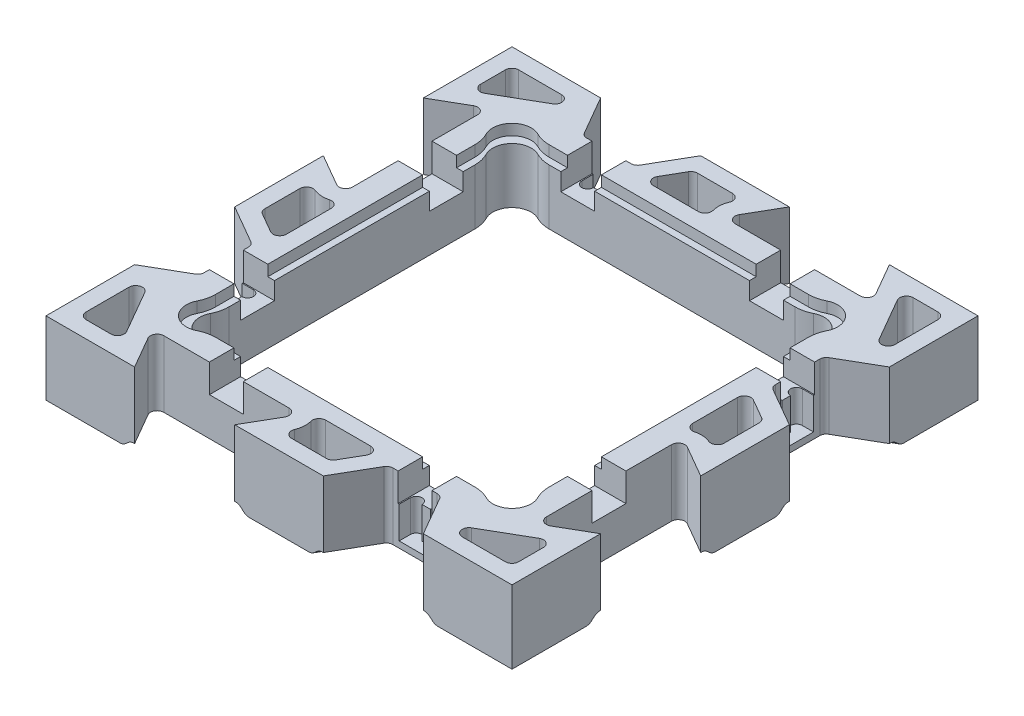
SolidWorks part; units mm, degrees
material "Macor"
ref_plane "Front Plane" through (0, 0, 0) normal (0, 0, 1) x (1, 0, 0)
ref_plane "Top Plane" through (0, 0, 0) normal (0, 1, 0) x (1, 0, 0)
ref_plane "Right Plane" through (0, 0, 0) normal (1, 0, 0) x (0, 0, -1)
sketch "Sketch1" plane through (0, 0, 0) normal (0, 1, 0) x (1, 0, 0)
  line L1 (-69.85, -69.85) -> (69.85, -69.85)
  line L2 (-69.85, -69.85) -> (-69.85, 69.85)
  line L3 (-69.85, 69.85) -> (69.85, 69.85)
  line L4 (69.85, -69.85) -> (69.85, 69.85)
  line L5 (-69.85, -69.85) -> (69.85, 69.85) construction
  line L6 (-69.85, 69.85) -> (69.85, -69.85) construction
  point P0 (0, 0)
  dimension "D1" = 139.7
extrude "Boss-Extrude1" add sketch "Sketch1" along normal mid plane 21.9
sketch "Sketch6" plane through (0, 10.95, 0) normal (0, 1, 0) x (1, 0, 0)
  line L0 (-48, 39.8683) -> (-48, -39.8683)
  line L1 (-48, -48) -> (48, -48) construction
  line L2 (-48, -48) -> (-48, 48) construction
  line L3 (-48, 48) -> (48, 48) construction
  line L4 (48, -48) -> (48, 48) construction
  line L5 (-48, -48) -> (48, 48) construction
  line L6 (-48, 48) -> (48, -48) construction
  line L7 (-39.8683, -48) -> (39.8683, -48)
  line L8 (39.8683, 48) -> (-39.8683, 48)
  line L9 (48, 39.8683) -> (48, -39.8683)
  arc A0 (-39.8683, 48) -> (-48, 39.8683) centre (-43.9341, 43.9341) ccw
  arc A1 (48, 39.8683) -> (39.8683, 48) centre (43.9341, 43.9341) ccw
  arc A2 (39.8683, -48) -> (48, -39.8683) centre (43.9341, -43.9341) ccw
  arc A3 (-48, -39.8683) -> (-39.8683, -48) centre (-43.9341, -43.9341) ccw
  point P0 (0, 0)
  point P21 (0, 0)
  dimension "D2" = 5.75
  dimension "D1" = 96
  dimension "D3" = 4
extrude "power_supply_component_depth" cut sketch "Sketch6" against normal through all both and the other way through all
ref_axis "Axis1" through (0, -25.4398, 0) along (0, 1, 0)
sketch "Sketch4" plane through (0, 10.95, 0) normal (0, 1, 0) x (1, 0, 0)
  line L0 (-43.2833, -69.85) -> (-50.5002, -57.35)
  line L1 (-69.85, -69.85) -> (69.85, -69.85) construction
  line L2 (-50.5002, -57.35) -> (-6.0665, -57.35)
  line L3 (-6.0665, -57.35) -> (-13.2833, -69.85)
  line L4 (-13.2833, -69.85) -> (-43.2833, -69.85)
  line L5 (43.2833, -69.85) -> (36.0665, -57.35)
  line L24 (43.2833, -69.85) -> (13.2833, -69.85)
  line L25 (-69.85, -69.85) -> (-43.2833, -69.85) construction
  line L26 (-13.2833, -69.85) -> (13.2833, -69.85) construction
  line L27 (43.2833, -69.85) -> (69.85, -69.85) construction
  line L28 (36.0665, -57.35) -> (20.5002, -57.35)
  line L30 (13.2833, -69.85) -> (20.5002, -57.35)
  dimension "D1" = 60
  dimension "D2" = 30
  dimension "D3" = 12.5
  dimension "D4" = 60
  dimension "D5" = 26.5667
extrude "Cut-Extrude6" cut sketch "Sketch4" against normal blind 22.4
sketch "Sketch8" plane through (0, 10.95, 0) normal (0, 1, 0) x (1, 0, 0)
  line L0 (-28.2833, -57.35) -> (-28.2833, -52.675) construction
  line L2 (28.2833, -57.35) -> (28.2833, -52.675) construction
  line L3 (36.0665, -57.35) -> (20.5002, -57.35) construction
  line L4 (-6.0665, -57.35) -> (-50.5002, -57.35) construction
  line L5 (-33.3633, -57.35) -> (-23.2033, -57.35)
  line L6 (-33.3633, -57.35) -> (-33.3633, -48)
  line L7 (-33.3633, -48) -> (-23.2033, -48)
  line L8 (-23.2033, -57.35) -> (-23.2033, -48)
  line L9 (-33.3633, -57.35) -> (-23.2033, -48) construction
  line L10 (-33.3633, -48) -> (-23.2033, -57.35) construction
  line L12 (23.2033, -57.35) -> (33.3633, -57.35)
  line L13 (23.2033, -57.35) -> (23.2033, -48)
  line L14 (23.2033, -48) -> (33.3633, -48)
  line L15 (33.3633, -57.35) -> (33.3633, -48)
  line L16 (23.2033, -57.35) -> (33.3633, -48) construction
  line L17 (23.2033, -48) -> (33.3633, -57.35) construction
  line L18 (-39.8683, -48) -> (39.8683, -48) construction
  dimension "D1" = 10.16
extrude "Cut-Extrude7" cut sketch "Sketch8" against normal blind 8.48
sketch "Sketch9" plane through (0, 2.47, 0) normal (0, 1, 0) x (1, 0, 0)
  line L0 (28.2833, -57.35) -> (28.2833, -55.6625) construction
  line L2 (27.0183, -53.975) -> (29.5483, -53.975)
  line L3 (23.5183, -53.975) -> (33.0483, -53.975) construction
  line L4 (23.5183, -53.975) -> (23.5183, -57.35)
  line L5 (23.5183, -57.35) -> (33.0483, -57.35)
  line L6 (33.0483, -53.975) -> (33.0483, -57.35)
  line L7 (23.5183, -53.975) -> (33.0483, -57.35) construction
  line L8 (23.5183, -57.35) -> (33.0483, -53.975) construction
  line L9 (23.2033, -57.35) -> (33.3633, -57.35) construction
  arc A0 (23.5183, -53.975) -> (27.0183, -53.975) centre (25.2683, -53.975) cw
  arc A1 (33.0483, -53.975) -> (29.5483, -53.975) centre (31.2983, -53.975) ccw
  dimension "D3" = 1.75
  dimension "D1" = 9.53
  dimension "D2" = 3.375
extrude "Cut-Extrude8" cut sketch "Sketch9" against normal blind 9.53
fillet "Fillet2" radius 2 4 edges at (20.5002, 0, 57.35) (36.0665, 0, 57.35) (-6.0665, 0, 57.35) (-50.5002, 0, 57.35)
pattern_circular "CirPattern5" count 4 over 360 about axis through (0, -25.4398, 0) along (0, 1, 0) of "Cut-Extrude6", "Cut-Extrude7", "Cut-Extrude8", "Fillet2"
sketch "Sketch10" plane through (0, 10.95, 0) normal (0, 1, 0) x (1, 0, 0)
  line L0 (-41.8683, 50) -> (41.8683, 50)
  line L1 (-50, -50) -> (50, -50) construction
  line L2 (-50, -50) -> (-50, 50) construction
  line L3 (-50, 50) -> (50, 50) construction
  line L4 (50, -50) -> (50, 50) construction
  line L5 (-50, -50) -> (50, 50) construction
  line L6 (-50, 50) -> (50, -50) construction
  line L7 (50, 41.8683) -> (50, -41.8683)
  line L8 (41.8683, -50) -> (-41.8683, -50)
  line L9 (-50, -41.8683) -> (-50, 41.8683)
  arc A0 (41.8683, 50) -> (50, 41.8683) centre (45.9341, 45.9341) cw
  arc A1 (50, -41.8683) -> (41.8683, -50) centre (45.9341, -45.9341) cw
  arc A2 (-41.8683, -50) -> (-50, -41.8683) centre (-45.9341, -45.9341) cw
  arc A3 (-50, 41.8683) -> (-41.8683, 50) centre (-45.9341, 45.9341) cw
  point P0 (0, 0)
  point P21 (0, 0)
  dimension "D2" = 5.75
  dimension "D1" = 100
  dimension "D3" = 4
extrude "Cut-Extrude9" cut sketch "Sketch10" against normal blind 3.25
fillet "Fillet3" radius 10 16 edges at (-50, 9.325, 41.8683) (-41.8683, 9.325, -50) (-50, 9.325, -41.8683) (50, 9.325, -41.8683) (41.8683, 9.325, -50) (-41.8683, 9.325, 50) (-39.8683, -1.625, -48) (39.8683, -1.625, -48) (48, -1.625, -39.8683) (48, -1.625, 39.8683) (-39.8683, -1.625, 48) (-48, -1.625, 39.8683) (-48, -1.625, -39.8683) (39.8683, -1.625, 48) (41.8683, 9.325, 50) (50, 9.325, 41.8683)
ref_plane "Plane1" through (19.4251, 0, 33.6453) normal (-0.5, 0, -0.866) x (-0.866, 0, 0.5)
sketch "Sketch11" plane through (19.4251, 0, 33.6453) normal (-0.5, 0, -0.866) x (-0.866, 0, 0.5)
  line L0 (72.4095, -10.95) -> (75.4095, -10.95)
  line L1 (75.4095, -10.95) -> (73.4095, -8.95)
  line L2 (73.4095, -8.95) -> (72.4095, -8.95)
  line L3 (72.4095, -10.95) -> (72.4095, 10.95) construction
  line L4 (72.4095, -8.95) -> (72.4095, -10.95)
  dimension "D1" = 3
  dimension "D2" = 2
  dimension "D3" = 45
  dimension "D4" = 1
sketch "Sketch12" plane through (0, -10.95, 0) normal (0, -1, 0) x (1, 0, 0)
  line L0 (-47.0361, 57.35) -> (-9.5306, 57.35) construction
  line L1 (-7.7985, 60.35) -> (-13.2833, 69.85) construction
  line L2 (-43.2833, 69.85) -> (-48.7682, 60.35) construction
  line L3 (-47.0361, 57.35) -> (-9.5306, 57.35)
  line L4 (-7.7985, 60.35) -> (-13.2833, 69.85)
  line L5 (-43.2833, 69.85) -> (-48.7682, 60.35)
  arc A0 (-9.5306, 57.35) -> (-7.7985, 60.35) centre (-9.5306, 59.35) ccw construction
  arc A1 (-48.7682, 60.35) -> (-47.0361, 57.35) centre (-47.0361, 59.35) ccw construction
  arc A2 (-9.5306, 57.35) -> (-7.7985, 60.35) centre (-9.5306, 59.35) ccw
  arc A3 (-48.7682, 60.35) -> (-47.0361, 57.35) centre (-47.0361, 59.35) ccw
sweep "Cut-Sweep1" cut profiles "Sketch11" path "Sketch12"
ref_plane "Plane2" through (-26.9251, 0, 46.6356) normal (0.5, 0, -0.866) x (-0.866, 0, -0.5)
sketch "Sketch13" plane through (-26.9251, 0, 46.6356) normal (0.5, 0, -0.866) x (-0.866, 0, -0.5)
  line L0 (-46.4287, -10.95) -> (-43.4287, -10.95)
  line L1 (-43.4287, -10.95) -> (-45.4287, -8.95)
  line L2 (-45.4287, -8.95) -> (-46.4287, -8.95)
  line L3 (-46.4287, -10.95) -> (-46.4287, 10.95) construction
  line L4 (-46.4287, -8.95) -> (-46.4287, -10.95)
  dimension "D1" = 45
  dimension "D2" = 2
  dimension "D3" = 3
sketch "Sketch14" plane through (0, -10.95, 0) normal (0, -1, 0) x (1, 0, 0)
  line L0 (36.6438, 58.35) -> (43.2833, 69.85) construction
  line L1 (21.6549, 57.35) -> (34.9118, 57.35) construction
  line L2 (13.2833, 69.85) -> (19.9229, 58.35) construction
  line L3 (36.6438, 58.35) -> (43.2833, 69.85)
  line L4 (21.6549, 57.35) -> (34.9118, 57.35)
  line L5 (13.2833, 69.85) -> (19.9229, 58.35)
  line L6 (13.2833, 69.85) -> (7.5098, 79.85)
  line L7 (43.2833, 69.85) -> (49.0568, 79.85)
  arc A0 (34.9118, 57.35) -> (36.6438, 58.35) centre (34.9118, 59.35) ccw construction
  arc A1 (19.9229, 58.35) -> (21.6549, 57.35) centre (21.6549, 59.35) ccw construction
  arc A2 (34.9118, 57.35) -> (36.6438, 58.35) centre (34.9118, 59.35) ccw
  arc A3 (19.9229, 58.35) -> (21.6549, 57.35) centre (21.6549, 59.35) ccw
  dimension "D1" = 10
sweep "Cut-Sweep2" cut profiles "Sketch13" path "Sketch14"
pattern_circular "CirPattern6" count 4 over 360 about axis through (0, -25.4398, 0) along (0, 1, 0) of "Cut-Sweep1", "Cut-Sweep2"
sketch "Sketch15" plane through (0, 0, 0) normal (0, 0, 1) x (1, 0, 0)
  line L0 (-48, -10.95) -> (-48, 7.7) construction
  line L1 (-48, -10.95) -> (-48, 7.7) construction
  line L2 (-48, -10.95) -> (-51, -10.95)
  line L3 (-51, -10.95) -> (-49, -8.95)
  line L4 (-49, -8.95) -> (-48, -8.95)
  line L5 (-48, -8.95) -> (-48, -10.95)
  dimension "D1" = 2
  dimension "D2" = 3
  dimension "D3" = 45
sketch "Sketch16" plane through (0, -10.95, 0) normal (0, -1, 0) x (1, 0, 0)
  line L0 (48, 36.848) -> (48, -36.848) construction
  line L1 (-36.848, 48) -> (36.848, 48) construction
  line L2 (-48, -36.848) -> (-48, 36.848) construction
  line L3 (36.848, -48) -> (-36.848, -48) construction
  line L4 (48, 36.848) -> (48, -36.848)
  line L5 (-36.848, 48) -> (36.848, 48)
  line L6 (-48, -36.848) -> (-48, 36.848)
  line L7 (36.848, -48) -> (-36.848, -48)
  arc A0 (48, -36.848) -> (49.0693, -41.3471) centre (58, -36.848) ccw construction
  arc A1 (49.0693, 41.3471) -> (48, 36.848) centre (58, 36.848) ccw construction
  arc A2 (49.0693, 41.3471) -> (41.3471, 49.0693) centre (43.9341, 43.9341) ccw construction
  arc A3 (36.848, 48) -> (41.3471, 49.0693) centre (36.848, 58) ccw construction
  arc A4 (-41.3471, 49.0693) -> (-36.848, 48) centre (-36.848, 58) ccw construction
  arc A5 (-41.3471, 49.0693) -> (-49.0693, 41.3471) centre (-43.9341, 43.9341) ccw construction
  arc A6 (-48, 36.848) -> (-49.0693, 41.3471) centre (-58, 36.848) ccw construction
  arc A7 (-49.0693, -41.3471) -> (-48, -36.848) centre (-58, -36.848) ccw construction
  arc A8 (-49.0693, -41.3471) -> (-41.3471, -49.0693) centre (-43.9341, -43.9341) ccw construction
  arc A9 (-36.848, -48) -> (-41.3471, -49.0693) centre (-36.848, -58) ccw construction
  arc A10 (41.3471, -49.0693) -> (36.848, -48) centre (36.848, -58) ccw construction
  arc A11 (41.3471, -49.0693) -> (49.0693, -41.3471) centre (43.9341, -43.9341) ccw construction
  arc A12 (48, -36.848) -> (49.0693, -41.3471) centre (58, -36.848) ccw
  arc A13 (49.0693, 41.3471) -> (48, 36.848) centre (58, 36.848) ccw
  arc A14 (49.0693, 41.3471) -> (41.3471, 49.0693) centre (43.9341, 43.9341) ccw
  arc A15 (36.848, 48) -> (41.3471, 49.0693) centre (36.848, 58) ccw
  arc A16 (-41.3471, 49.0693) -> (-36.848, 48) centre (-36.848, 58) ccw
  arc A17 (-41.3471, 49.0693) -> (-49.0693, 41.3471) centre (-43.9341, 43.9341) ccw
  arc A18 (-48, 36.848) -> (-49.0693, 41.3471) centre (-58, 36.848) ccw
  arc A19 (-49.0693, -41.3471) -> (-48, -36.848) centre (-58, -36.848) ccw
  arc A20 (-49.0693, -41.3471) -> (-41.3471, -49.0693) centre (-43.9341, -43.9341) ccw
  arc A21 (-36.848, -48) -> (-41.3471, -49.0693) centre (-36.848, -58) ccw
  arc A22 (41.3471, -49.0693) -> (36.848, -48) centre (36.848, -58) ccw
  arc A23 (41.3471, -49.0693) -> (49.0693, -41.3471) centre (43.9341, -43.9341) ccw
sweep "Cut-Sweep3" cut profiles "Sketch15" path "Sketch16"
fillet "Fillet4" radius 2 122 edges at (-46.3144, -10.95, -69.1) (-42.5616, -10.95, -62.6) (-37.4118, -10.95, -55.0199) (-13.572, -10.95, -63.35) (-19.1549, -10.95, -55.0199) (-44.2937, -8.95, -69.6) (-40.8296, -8.95, -63.6) (-36.4118, -8.95, -56.7519) (-15.5927, -8.95, -63.85) (-20.1549, -8.95, -56.7519) (49.0568, -10.95, -65.85) (51.3662, -10.95, -56.85) (7.5098, -10.95, -65.85) (5.2004, -10.95, -56.85) (47.0361, -8.95, -65.35) (49.6342, -8.95, -57.85) (9.5306, -8.95, -65.35) (6.9325, -8.95, -57.85) (69.1, -10.95, -46.3144) (62.6, -10.95, -42.5616) (55.0199, -10.95, -37.4118) (54.35, -10.95, -28.2833) (55.0199, -10.95, -19.1549) (69.6, -8.95, -44.2937) (63.6, -8.95, -40.8296) (56.7519, -8.95, -36.4118) (56.35, -8.95, -28.2833) (56.7519, -8.95, -20.1549) (65.85, -10.95, 7.5098) (56.85, -10.95, 5.2004) (54.35, -10.95, 28.2833) (56.85, -10.95, 51.3662) (65.35, -8.95, 9.5306) (57.85, -8.95, 6.9325) (56.35, -8.95, 28.2833) (57.85, -8.95, 49.6342) (46.3144, -10.95, 69.1) (42.5616, -10.95, 62.6) (37.4118, -10.95, 55.0199) (28.2833, -10.95, 54.35) (19.1549, -10.95, 55.0199) (44.2937, -8.95, 69.6) (40.8296, -8.95, 63.6) (36.4118, -8.95, 56.7519) (28.2833, -8.95, 56.35) (20.1549, -8.95, 56.7519) (-49.0568, -10.95, 65.85) (-51.3662, -10.95, 56.85) (-28.2833, -10.95, 54.35) (-7.5098, -10.95, 65.85) (-47.0361, -8.95, 65.35) (-49.6342, -8.95, 57.85) (-28.2833, -8.95, 56.35) (-9.5306, -8.95, 65.35) (-49.2439, -8.95, -38.929) (-48.7071, -8.95, -48.7071) (-38.929, -8.95, -49.2439) (0, -8.95, -49) (38.929, -8.95, -49.2439) (48.7071, -8.95, -48.7071) (49.2439, -8.95, -38.929) (49, -8.95, 0) (49.2439, -8.95, 38.929) (48.7071, -8.95, 48.7071) (38.929, -8.95, 49.2439) (0, -8.95, 49) (-38.929, -8.95, 49.2439) (-48.7071, -8.95, 48.7071) (-49.2439, -8.95, 38.929) (-49, -8.95, 18.424) (-51.1897, -10.95, -38.4665) (-50.1213, -10.95, -50.1213) (-38.4665, -10.95, -51.1897) (0, -10.95, -51) (38.4665, -10.95, -51.1897) (50.1213, -10.95, -50.1213) (51.1897, -10.95, -38.4665) (51, -10.95, 0) (51.1897, -10.95, 38.4665) (50.1213, -10.95, 50.1213) (38.4665, -10.95, 51.1897) (0, -10.95, 51) (-38.4665, -10.95, 51.1897) (-50.1213, -10.95, 50.1213) (-51.1897, -10.95, 38.4665) (-51, -10.95, 18.424) (-65.85, -10.95, -49.0568) (-56.85, -10.95, -51.3662) (-54.35, -10.95, -28.2833) (-65.85, -10.95, -7.5098) (-63.35, -10.95, 13.572) (-55.0199, -10.95, 19.1549) (-69.1, -10.95, 46.3144) (-62.6, -10.95, 42.5616) (-55.0199, -10.95, 37.4118) (-63.85, -8.95, 15.5927) (-56.7519, -8.95, 20.1549) (-69.6, -8.95, 44.2937) (-63.6, -8.95, 40.8296) (-56.7519, -8.95, 36.4118) (-65.35, -8.95, -47.0361) (-57.85, -8.95, -49.6342) (-65.35, -8.95, -9.5306) (-57.85, -8.95, -6.9325) (-28.2833, -10.95, -54.35) (-28.2833, -8.95, -56.35) (28.2833, -10.95, -54.35) (28.2833, -8.95, -56.35) (63.35, -10.95, -13.572) (63.85, -8.95, -15.5927) (65.85, -10.95, 49.0568) (65.35, -8.95, 47.0361) (13.572, -10.95, 63.35) (15.5927, -8.95, 63.85) (-5.2004, -10.95, 56.85) (-6.9325, -8.95, 57.85) (-49, -8.95, -18.424) (-51, -10.95, -18.424) (-56.85, -10.95, -5.2004) (-54.35, -10.95, 28.2833) (-56.35, -8.95, 28.2833) (-56.35, -8.95, -28.2833)
sketch "Sketch17" plane through (0, 10.95, 0) normal (0, 1, 0) x (1, 0, 0)
  line L0 (62.85, 64.85) -> (55.4077, 64.85)
  line L1 (53.6756, 61.85) -> (61.1179, 48.9595)
  line L2 (64.85, 49.9595) -> (64.85, 62.85)
  line L4 (64.85, 10.3966) -> (55, 16.0835)
  line L5 (55, 16.0835) -> (55, -4.0463)
  line L23 (55, 16.1706) -> (55, -4.0463)
  line L24 (53.0983, 62.85) -> (63.2588, 45.2514) construction
  line L25 (62.85, -3.4684) -> (64.85, -4.6231)
  line L26 (64.85, -4.6231) -> (64.85, 10.3966)
  line L27 (64.85, 10.3966) -> (55.85, 15.5927)
  line L28 (55, 16.1706) -> (55, -4.0463) construction
  line L29 (62.85, -3.4684) -> (64.85, -4.6231)
  line L30 (64.85, -4.6231) -> (64.85, 10.3966)
  line L31 (64.85, 10.3966) -> (55.85, 15.5927) construction
  line L34 (55.85, 40.9739) -> (64.85, 46.1701)
  line L35 (64.85, 46.1701) -> (64.85, 64.85)
  line L36 (64.85, 64.85) -> (51.9436, 64.85)
  line L37 (51.9436, 64.85) -> (53.0983, 62.85)
  line L38 (63.2588, 45.2514) -> (64.85, 46.1701) construction
  line L39 (64.85, 46.1701) -> (64.85, 64.85) construction
  line L40 (64.85, 64.85) -> (51.9436, 64.85) construction
  line L41 (51.9436, 64.85) -> (53.0983, 62.85) construction
  arc A0 (55.4077, 64.85) -> (53.6756, 61.85) centre (55.4077, 62.85) ccw
  arc A1 (64.85, 62.85) -> (62.85, 64.85) centre (62.85, 62.85) ccw
  arc A2 (64.85, 49.9595) -> (61.1179, 48.9595) centre (62.85, 49.9595) cw
  arc A7 (62.85, -3.4684) -> (55, -4.0463) centre (59.35, -9.5306) ccw
  arc A8 (55, 16.1706) -> (55.85, 15.5927) centre (59.35, 21.6549) ccw
  arc A9 (62.85, -3.4684) -> (55, -4.0463) centre (59.35, -9.5306) ccw
  arc A15 (55.5346, 41.0975) -> (52.2248, 54.6514) centre (45.9341, 45.9341) ccw
  arc A16 (55.5346, 41.0975) -> (55.3342, 40.6453) centre (60, 38.848) ccw
  arc A17 (55.85, 40.9739) -> (55.3342, 40.6453) centre (59.35, 34.9118) ccw
  arc A18 (52.2248, 54.6514) -> (53.0983, 62.85) centre (47.0361, 59.35) ccw
  dimension "D2" = 2
  dimension "D1" = 5
  dimension "D3" = 5
extrude "Cut-Extrude10" cut sketch "Sketch17" against normal offset from surface (16.9 mm away) 5 up to face at (0, -10.95, 0)
fillet "Fillet5" radius 2 4 edges at (64.85, 2.5, 4.6231) (64.85, 2.5, -10.3966) (55, 2.5, -16.0835) (55, 2.5, 4.0463)
pattern_circular "CirPattern7" count 4 over 360 about axis through (0, -25.4398, 0) along (0, 1, 0) of "Fillet5", "Cut-Extrude10"
